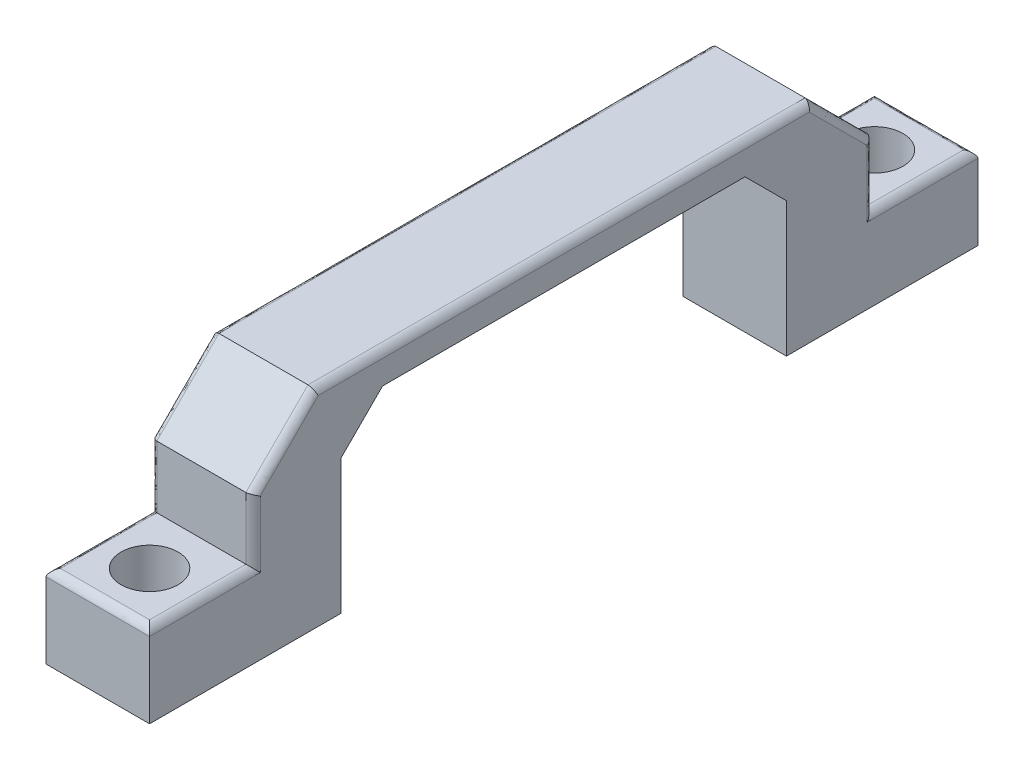
SolidWorks part; units mm, degrees
ref_plane "Front Plane" through (0, 0, 0) normal (0, 0, 1) x (1, 0, 0)
ref_plane "Top Plane" through (0, 0, 0) normal (0, 1, 0) x (1, 0, 0)
ref_plane "Right Plane" through (0, 0, 0) normal (1, 0, 0) x (0, 0, -1)
sketch "Sketch1" plane through (0, 0, 0) normal (0, 1, 0) x (1, 0, 0)
  line L1 (-5, -40) -> (5, -40)
  line L2 (-5, -40) -> (-5, 40)
  line L3 (-5, 40) -> (5, 40)
  line L4 (5, -40) -> (5, 40)
  line L5 (-5, -40) -> (5, 40) construction
  line L6 (-5, 40) -> (5, -40) construction
  point P0 (0, 0)
  dimension "D1" = 10
  dimension "D2" = 80
extrude "Boss-Extrude1" add sketch "Sketch1" along normal blind 20
sketch "Sketch2" plane through (0, 20, 0) normal (0, 1, 0) x (1, 0, 0)
  line L0 (-5.5, 0) -> (5.5, 0) construction
  line L2 (-5, 40) -> (-5, -40) construction
  circle A0 centre (0, 35) radius 2.75
  circle A1 centre (0, -35) radius 2.75
  dimension "D1" = 5.5
  dimension "D2" = 5
  dimension "D3" = 35
extrude "Cut-Extrude1" cut sketch "Sketch2" against normal through all
sketch "Sketch4" plane through (0, 0, 0) normal (0, -1, 0) x (1, 0, 0)
  line L0 (5, 40) -> (5, -40) construction
  line L1 (-5, -21.5) -> (5, -21.5)
  line L2 (-5, -21.5) -> (-5, 21.5)
  line L3 (-5, 21.5) -> (5, 21.5)
  line L4 (5, -21.5) -> (5, 21.5)
  line L5 (-5, -21.5) -> (5, 21.5) construction
  line L6 (-5, 21.5) -> (5, -21.5) construction
  point P0 (0, 0)
  dimension "D1" = 43
extrude "Cut-Extrude2" cut sketch "Sketch4" against normal blind 17
chamfer "Chamfer1" distance 4 angle 45 2 edges at (0, 17, 21.5) (0, 17, -21.5)
sketch "Sketch5" plane through (0, 20, 0) normal (0, 1, 0) x (1, 0, 0)
  line L1 (-5, 30) -> (5, 30)
  line L2 (-5, 30) -> (-5, 40)
  line L3 (-5, 40) -> (5, 40)
  line L4 (5, 30) -> (5, 40)
  line L5 (-5, 30) -> (5, 40) construction
  line L6 (-5, 40) -> (5, 30) construction
  point P1 (0, 35)
  dimension "D1" = 10
  dimension "D2" = 10
extrude "Cut-Extrude3" cut sketch "Sketch5" against normal blind 12
mirror "Mirror1" about plane through (0, 0, 0) normal (0, 0, 1) of "Cut-Extrude3"
chamfer "Chamfer2" distance 6 angle 45 2 edges at (0, 20, 30) (0, 20, -30)
fillet "Fillet1" radius 0.7 16 edges at (-5, 8, 35) (0, 8, 40) (5, 8, 35) (5, 11, 30) (5, 17, 27) (-5, 11, 30) (-5, 17, 27) (-5, 20, 0) (-5, 17, -27) (-5, 11, -30) (-5, 8, -35) (0, 8, -40) (5, 8, -35) (5, 11, -30) (5, 17, -27) (5, 20, 0) conic rho 0.25
